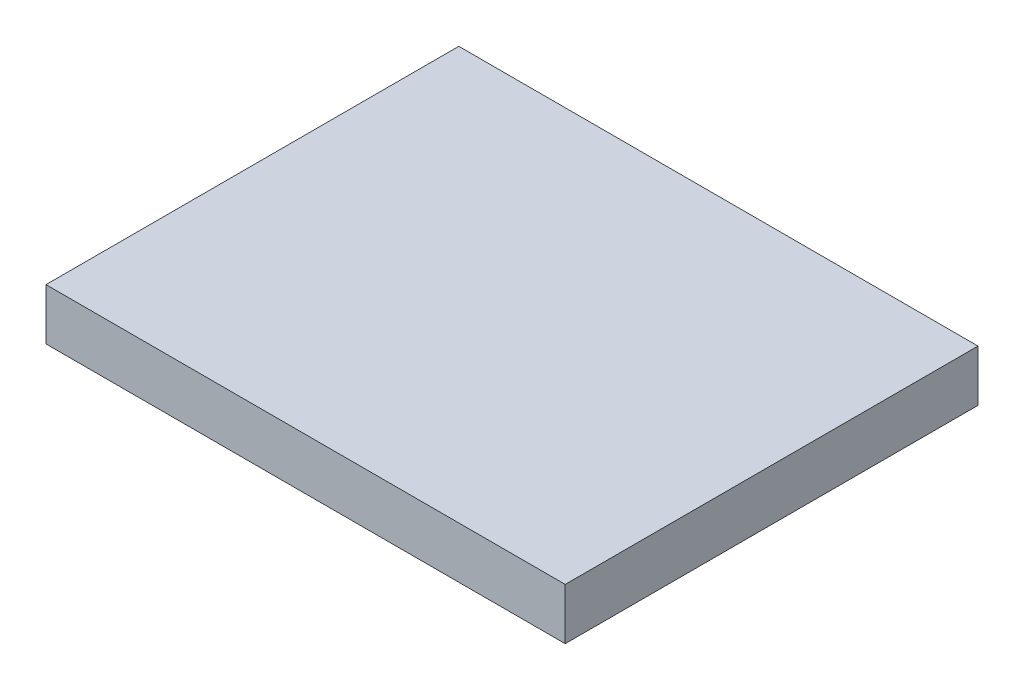
SolidWorks part; units mm, degrees
ref_plane "Front Plane" through (0, 0, 0) normal (0, 0, 1) x (1, 0, 0)
ref_plane "Top Plane" through (0, 0, 0) normal (0, 1, 0) x (1, 0, 0)
ref_plane "Right Plane" through (0, 0, 0) normal (1, 0, 0) x (0, 0, -1)
sketch "Sketch1" plane through (0, 0, 0) normal (0, 1, 0) x (1, 0, 0)
  line L1 (0, 0) -> (283, 0)
  line L2 (0, 0) -> (0, 225)
  line L3 (0, 225) -> (283, 225)
  line L4 (283, 0) -> (283, 225)
  dimension "D1" = 225
  dimension "D2" = 283
extrude "Boss-Extrude1" add sketch "Sketch1" along normal blind 28
sketch "Sketch2" plane through (0, 0, 0) normal (0, -1, 0) x (1, 0, 0)
  line L0 (0, 0) -> (283, 0) construction
  line L1 (283, -225) -> (0, -225) construction
  line L2 (0, -225) -> (0, 0) construction
  line L3 (283, 0) -> (283, -225) construction
  circle A0 centre (25, -25) radius 10
  circle A1 centre (25, -200) radius 10
  circle A2 centre (258, -200) radius 10
  circle A3 centre (258, -25) radius 10
  dimension "D1" = 20
  dimension "D10" = 20
  dimension "D11" = 20
  dimension "D12" = 20
  dimension "D2" = 25
  dimension "D3" = 25
  dimension "D4" = 25
  dimension "D5" = 25
  dimension "D6" = 25
  dimension "D7" = 25
  dimension "D8" = 25
  dimension "D9" = 25
extrude "Boss-Extrude2" add sketch "Sketch2" along normal blind 6.5
equation "\"Length\"= 283mm"
equation "\"Width\"= 225mm"
equation "\"WallThickness\"= 12.5mm"
equation "\"D1@Sketch1\"=\"Width\""
equation "\"D2@Sketch1\"=\"Length\""
equation "\"UpperWaterJacketThickness\"= 28mm"
equation "\"D1@Boss-Extrude1\"=\"UpperWaterJacketThickness\""
equation "\"UpperWaterJacketPegDiameter\"=20"
equation "\"D1@Sketch2\"=\"UpperWaterJacketPegDiameter\""
equation "\"UpperWaterJacketPegDistance\"=2.5"
equation "\"D2@Sketch2\"=\"WallThickness\"+\"UpperWaterJacketPegDiameter\"/2+\"UpperWaterJacketPegDistance\""
equation "\"D3@Sketch2\"=\"WallThickness\"+\"UpperWaterJacketPegDiameter\"/2+\"UpperWaterJacketPegDistance\""
equation "\"D4@Sketch2\"=\"WallThickness\"+\"UpperWaterJacketPegDiameter\"/2+\"UpperWaterJacketPegDistance\""
equation "\"D5@Sketch2\"=\"WallThickness\"+\"UpperWaterJacketPegDiameter\"/2+\"UpperWaterJacketPegDistance\""
equation "\"D6@Sketch2\"=\"WallThickness\"+\"UpperWaterJacketPegDiameter\"/2+\"UpperWaterJacketPegDistance\""
equation "\"D7@Sketch2\"=\"WallThickness\"+\"UpperWaterJacketPegDiameter\"/2+\"UpperWaterJacketPegDistance\""
equation "\"D8@Sketch2\"=\"WallThickness\"+\"UpperWaterJacketPegDiameter\"/2+\"UpperWaterJacketPegDistance\""
equation "\"D9@Sketch2\"=\"WallThickness\"+\"UpperWaterJacketPegDiameter\"/2+\"UpperWaterJacketPegDistance\""
equation "\"D10@Sketch2\"=\"UpperWaterJacketPegDiameter\""
equation "\"D11@Sketch2\"=\"UpperWaterJacketPegDiameter\""
equation "\"D12@Sketch2\"=\"UpperWaterJacketPegDiameter\""
equation "\"UpperWaterJacketPegHeight\"=6.5"
equation "\"D1@Boss-Extrude2\"=\"UpperWaterJacketPegHeight\""
equation "\"SpacerHeight\"= 80.2mm"
equation "\"SpacerCornerWidth\"= 10mm"
equation "\"SpacerCornerHeight\"= 60.16mm"
equation "\"SpacerPegDiameter\"= 10mm"
equation "\"SpacerPegHeight\"= 10mm"
equation "\"TubingShort\"= 110mm"
equation "\"TubingLong\"= 175mm"
equation "\"PlateLength\"= 252mm"
equation "\"PlateWidth\"= 190mm"
equation "\"PlateHoleDiameter\"= 5.9mm"
equation "\"PlateHoleBottom\"= 2mm"
equation "\"PlateHoleSide\"= 1.55mm"
equation "\"PlateHoleSpacing\"= 3.1mm"
equation "\"PlateThickness\"= 1.55mm"
equation "\"ReservoirBottom\"= 12.5mm"
equation "\"ReservoirSupportWidth\"= 12mm"
equation "\"ReservoirSupportHeight\"= 15.1mm"
equation "\"ReservoirSupportPlacementHeight\"= 50mm"
equation "\"ReservoirHoleDiameter\"= 12.7mm"
equation "\"ReservoirHoleRight\"= 25mm"
equation "\"ReservoirHoleTop\"= \"ReservoirSupportPlacementHeight\""
equation "\"ReservoirHeight\"= 90mm"
equation "\"ReservoirPortBottom\"= 4mm"
equation "\"ReservoirPortTop\"= 10mm"
equation "\"ReservoirPortWidth\"= 101mm"
equation "\"CustomSpacerWallThickness\"= 6.35mm"
equation "\"CustomSpacerHeight\"= 5in"
equation "\"CustomSpacerRodHoleHeight\"= .75in"
equation "\"CustomSpacerRodHoleDiameter\"= .3125in"
equation "\"ScrewBlockSide\"= .5in"
equation "\"ScrewBlockUpperHeight\"= 16mm"
equation "\"ScrewBlockLowerHeight\"= 16mm"
equation "\"InternalLength\"= \"Length\" - ( 2 * \"WallThickness\" )"
equation "\"InternalWidth\"= \"Width\" - ( 2 * \"WallThickness\" )"
